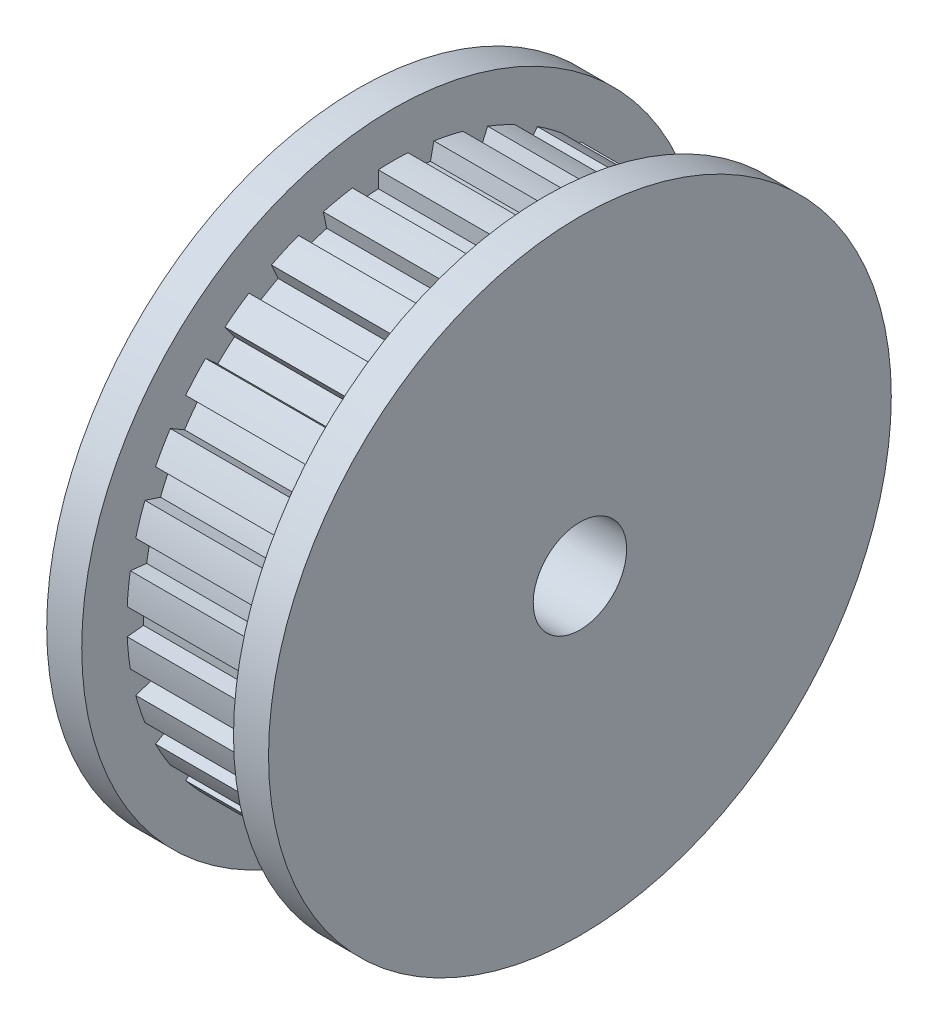
SolidWorks part; units mm, degrees
material "Default"
ref_plane "Top" through (0, 0, 0) normal (0, 0, 1) x (1, 0, 0)
ref_plane "Right" through (0, 0, 0) normal (0, 1, 0) x (1, 0, 0)
ref_plane "Front" through (0, 0, 0) normal (1, 0, 0) x (0, 0, -1)
ref_plane "Plane1" through (-64.6347, 0, 0) normal (-1, 0, 0) x (0, 0, 1)
sketch "Sketch2" plane through (-64.6347, 0, 0) normal (-1, 0, 0) x (0, 0, 1)
  circle A0 centre (18.1528, -99.414) radius 13.335
  circle A1 centre (18.1528, -99.414) radius 2
  dimension "D1" = 4
  dimension "D2" = 26.67
extrude "Boss-Extrude1" add sketch "Sketch2" against normal up to surface (9.5 mm away)
ref_axis "Axis1" through (-22.4133, -99.414, 18.1528) along (-1, 0, 0)
ref_plane "Plane2" through (0, 0, 18.1528) normal (0, 0, -1) x (-1, 0, 0)
sketch "Sketch4" plane through (0, 0, 18.1528) normal (0, 0, -1) x (-1, 0, 0)
  line L0 (52.4933, -99.414) -> (71.4445, -99.414) construction
  line L1 (22.4133, -99.414) -> (89.3613, -99.414) construction
  line L2 (56.6347, -84.904) -> (63.1347, -84.904)
  line L3 (63.1347, -84.904) -> (63.1347, -88.714)
  line L4 (56.6347, -84.904) -> (56.6347, -88.714)
  line L5 (56.6347, -88.714) -> (63.1347, -88.714)
  line L6 (59.8847, -86.714) -> (59.8847, -89.6647) construction
  point P12 (59.8847, -88.714)
  dimension "D1" = 3.81
  dimension "D2" = 6.5
  dimension "D3" = 10.7
revolve "Cut-Revolve1" cut sketch "Sketch4" angle 360 about L0
sketch "Sketch5" plane through (-63.1347, 0, 0) normal (1, 0, 0) x (0, 0, -1)
  line L0 (-18.1528, -99.414) -> (-18.1528, -85.2895) construction
  line L1 (-18.7878, -88.0312) -> (-18.7878, -88.7329)
  line L2 (-17.5178, -88.0312) -> (-17.5178, -88.7329)
  line L3 (-16.4073, -88.148) -> (-16.5532, -88.8343)
  line L4 (-15.165, -88.412) -> (-15.3109, -89.0983)
  line L5 (-14.1031, -88.7571) -> (-14.3885, -89.3981)
  line L6 (-12.9429, -89.2736) -> (-13.2283, -89.9146)
  line L7 (-11.9759, -89.8319) -> (-12.3883, -90.3996)
  line L8 (-10.9484, -90.5784) -> (-11.3608, -91.1461)
  line L9 (-10.1186, -91.3256) -> (-10.64, -91.7951)
  line L10 (-9.2688, -92.2694) -> (-9.7902, -92.7389)
  line L11 (-8.6125, -93.1727) -> (-9.2201, -93.5235)
  line L12 (-7.9775, -94.2726) -> (-8.5851, -94.6234)
  line L13 (-7.5233, -95.2926) -> (-8.1906, -95.5095)
  line L14 (-7.1309, -96.5005) -> (-7.7982, -96.7173)
  line L15 (-6.8987, -97.5927) -> (-7.5965, -97.666)
  line L16 (-6.766, -98.8557) -> (-7.4638, -98.9291)
  line L17 (-6.766, -99.9723) -> (-7.4638, -99.899)
  line L18 (-6.8987, -101.2354) -> (-7.5965, -101.162)
  line L19 (-7.1309, -102.3276) -> (-7.7982, -102.1108)
  line L20 (-7.5233, -103.5354) -> (-8.1906, -103.3186)
  line L21 (-7.9775, -104.5555) -> (-8.5851, -104.2047)
  line L22 (-8.6125, -105.6554) -> (-9.2201, -105.3045)
  line L23 (-9.2688, -106.5587) -> (-9.7902, -106.0892)
  line L24 (-10.1186, -107.5025) -> (-10.64, -107.033)
  line L25 (-10.9484, -108.2497) -> (-11.3608, -107.682)
  line L26 (-11.9759, -108.9962) -> (-12.3883, -108.4285)
  line L27 (-12.9429, -109.5545) -> (-13.2283, -108.9135)
  line L28 (-14.1031, -110.071) -> (-14.3885, -109.43)
  line L29 (-15.165, -110.4161) -> (-15.3109, -109.7298)
  line L30 (-16.4073, -110.6801) -> (-16.5532, -109.9938)
  line L31 (-17.5178, -110.7968) -> (-17.5178, -110.0952)
  line L32 (-18.7878, -110.7968) -> (-18.7878, -110.0952)
  line L33 (-19.8983, -110.6801) -> (-19.7524, -109.9938)
  line L34 (-21.1405, -110.4161) -> (-20.9946, -109.7298)
  line L35 (-22.2025, -110.071) -> (-21.9171, -109.43)
  line L36 (-23.3627, -109.5545) -> (-23.0773, -108.9135)
  line L37 (-24.3297, -108.9962) -> (-23.9173, -108.4285)
  line L38 (-25.3571, -108.2497) -> (-24.9447, -107.682)
  line L39 (-26.1869, -107.5025) -> (-25.6655, -107.033)
  line L40 (-27.0367, -106.5587) -> (-26.5153, -106.0892)
  line L41 (-27.6931, -105.6554) -> (-27.0854, -105.3045)
  line L42 (-28.3281, -104.5555) -> (-27.7204, -104.2047)
  line L43 (-28.7822, -103.5354) -> (-28.1149, -103.3186)
  line L44 (-29.1747, -102.3276) -> (-28.5074, -102.1108)
  line L45 (-29.4068, -101.2354) -> (-28.709, -101.162)
  line L46 (-29.5396, -99.9723) -> (-28.8418, -99.899)
  line L47 (-29.5396, -98.8557) -> (-28.8418, -98.9291)
  line L48 (-29.4068, -97.5927) -> (-28.709, -97.666)
  line L49 (-29.1747, -96.5005) -> (-28.5074, -96.7173)
  line L50 (-28.7822, -95.2926) -> (-28.1149, -95.5095)
  line L51 (-28.3281, -94.2726) -> (-27.7204, -94.6234)
  line L52 (-27.6931, -93.1727) -> (-27.0854, -93.5235)
  line L53 (-27.0367, -92.2694) -> (-26.5153, -92.7389)
  line L54 (-26.1869, -91.3256) -> (-25.6655, -91.7951)
  line L55 (-25.3571, -90.5784) -> (-24.9447, -91.1461)
  line L56 (-24.3297, -89.8319) -> (-23.9173, -90.3996)
  line L57 (-23.3627, -89.2736) -> (-23.0773, -89.9146)
  line L58 (-22.2025, -88.7571) -> (-21.9171, -89.3981)
  line L59 (-21.1405, -88.412) -> (-20.9946, -89.0983)
  line L60 (-19.8983, -88.148) -> (-19.7524, -88.8343)
  arc A0 (-17.5178, -88.7329) -> (-18.7878, -88.7329) centre (-18.1528, -99.414) ccw
  arc A1 (-17.5178, -88.0312) -> (-18.7878, -88.0312) centre (-18.1528, -99.414) ccw
  arc A2 (-15.3109, -89.0983) -> (-16.5532, -88.8343) centre (-18.1528, -99.414) ccw
  arc A3 (-15.165, -88.412) -> (-16.4073, -88.148) centre (-18.1528, -99.414) ccw
  arc A4 (-13.2283, -89.9146) -> (-14.3885, -89.3981) centre (-18.1528, -99.414) ccw
  arc A5 (-12.9429, -89.2736) -> (-14.1031, -88.7571) centre (-18.1528, -99.414) ccw
  arc A6 (-11.3608, -91.1461) -> (-12.3883, -90.3996) centre (-18.1528, -99.414) ccw
  arc A7 (-10.9484, -90.5784) -> (-11.9759, -89.8319) centre (-18.1528, -99.414) ccw
  arc A8 (-9.7902, -92.7389) -> (-10.64, -91.7951) centre (-18.1528, -99.414) ccw
  arc A9 (-9.2688, -92.2694) -> (-10.1186, -91.3256) centre (-18.1528, -99.414) ccw
  arc A10 (-8.5851, -94.6234) -> (-9.2201, -93.5235) centre (-18.1528, -99.414) ccw
  arc A11 (-7.9775, -94.2726) -> (-8.6125, -93.1727) centre (-18.1528, -99.414) ccw
  arc A12 (-7.7982, -96.7173) -> (-8.1906, -95.5095) centre (-18.1528, -99.414) ccw
  arc A13 (-7.1309, -96.5005) -> (-7.5233, -95.2926) centre (-18.1528, -99.414) ccw
  arc A14 (-7.4638, -98.9291) -> (-7.5965, -97.666) centre (-18.1528, -99.414) ccw
  arc A15 (-6.766, -98.8557) -> (-6.8987, -97.5927) centre (-18.1528, -99.414) ccw
  arc A16 (-7.5965, -101.162) -> (-7.4638, -99.899) centre (-18.1528, -99.414) ccw
  arc A17 (-6.8987, -101.2354) -> (-6.766, -99.9723) centre (-18.1528, -99.414) ccw
  arc A18 (-8.1906, -103.3186) -> (-7.7982, -102.1108) centre (-18.1528, -99.414) ccw
  arc A19 (-7.5233, -103.5354) -> (-7.1309, -102.3276) centre (-18.1528, -99.414) ccw
  arc A20 (-9.2201, -105.3045) -> (-8.5851, -104.2047) centre (-18.1528, -99.414) ccw
  arc A21 (-8.6125, -105.6554) -> (-7.9775, -104.5555) centre (-18.1528, -99.414) ccw
  arc A22 (-10.64, -107.033) -> (-9.7902, -106.0892) centre (-18.1528, -99.414) ccw
  arc A23 (-10.1186, -107.5025) -> (-9.2688, -106.5587) centre (-18.1528, -99.414) ccw
  arc A24 (-12.3883, -108.4285) -> (-11.3608, -107.682) centre (-18.1528, -99.414) ccw
  arc A25 (-11.9759, -108.9962) -> (-10.9484, -108.2497) centre (-18.1528, -99.414) ccw
  arc A26 (-14.3885, -109.43) -> (-13.2283, -108.9135) centre (-18.1528, -99.414) ccw
  arc A27 (-14.1031, -110.071) -> (-12.9429, -109.5545) centre (-18.1528, -99.414) ccw
  arc A28 (-16.5532, -109.9938) -> (-15.3109, -109.7298) centre (-18.1528, -99.414) ccw
  arc A29 (-16.4073, -110.6801) -> (-15.165, -110.4161) centre (-18.1528, -99.414) ccw
  arc A30 (-18.7878, -110.0952) -> (-17.5178, -110.0952) centre (-18.1528, -99.414) ccw
  arc A31 (-18.7878, -110.7968) -> (-17.5178, -110.7968) centre (-18.1528, -99.414) ccw
  arc A32 (-20.9946, -109.7298) -> (-19.7524, -109.9938) centre (-18.1528, -99.414) ccw
  arc A33 (-21.1405, -110.4161) -> (-19.8983, -110.6801) centre (-18.1528, -99.414) ccw
  arc A34 (-23.0773, -108.9135) -> (-21.9171, -109.43) centre (-18.1528, -99.414) ccw
  arc A35 (-23.3627, -109.5545) -> (-22.2025, -110.071) centre (-18.1528, -99.414) ccw
  arc A36 (-24.9447, -107.682) -> (-23.9173, -108.4285) centre (-18.1528, -99.414) ccw
  arc A37 (-25.3571, -108.2497) -> (-24.3297, -108.9962) centre (-18.1528, -99.414) ccw
  arc A38 (-26.5153, -106.0892) -> (-25.6655, -107.033) centre (-18.1528, -99.414) ccw
  arc A39 (-27.0367, -106.5587) -> (-26.1869, -107.5025) centre (-18.1528, -99.414) ccw
  circle A40 centre (-18.1528, -99.414) radius 10.7 construction
  arc A41 (-27.7204, -104.2047) -> (-27.0854, -105.3045) centre (-18.1528, -99.414) ccw
  arc A42 (-28.3281, -104.5555) -> (-27.6931, -105.6554) centre (-18.1528, -99.414) ccw
  arc A43 (-28.5074, -102.1108) -> (-28.1149, -103.3186) centre (-18.1528, -99.414) ccw
  arc A44 (-29.1747, -102.3276) -> (-28.7822, -103.5354) centre (-18.1528, -99.414) ccw
  arc A45 (-28.8418, -99.899) -> (-28.709, -101.162) centre (-18.1528, -99.414) ccw
  arc A46 (-29.5396, -99.9723) -> (-29.4068, -101.2354) centre (-18.1528, -99.414) ccw
  arc A47 (-28.709, -97.666) -> (-28.8418, -98.9291) centre (-18.1528, -99.414) ccw
  arc A48 (-29.4068, -97.5927) -> (-29.5396, -98.8557) centre (-18.1528, -99.414) ccw
  arc A49 (-28.1149, -95.5095) -> (-28.5074, -96.7173) centre (-18.1528, -99.414) ccw
  arc A50 (-28.7822, -95.2926) -> (-29.1747, -96.5005) centre (-18.1528, -99.414) ccw
  arc A51 (-27.0854, -93.5235) -> (-27.7204, -94.6234) centre (-18.1528, -99.414) ccw
  arc A52 (-27.6931, -93.1727) -> (-28.3281, -94.2726) centre (-18.1528, -99.414) ccw
  arc A53 (-25.6655, -91.7951) -> (-26.5153, -92.7389) centre (-18.1528, -99.414) ccw
  arc A54 (-26.1869, -91.3256) -> (-27.0367, -92.2694) centre (-18.1528, -99.414) ccw
  arc A55 (-23.9173, -90.3996) -> (-24.9447, -91.1461) centre (-18.1528, -99.414) ccw
  arc A56 (-24.3297, -89.8319) -> (-25.3571, -90.5784) centre (-18.1528, -99.414) ccw
  arc A57 (-21.9171, -89.3981) -> (-23.0773, -89.9146) centre (-18.1528, -99.414) ccw
  arc A58 (-22.2025, -88.7571) -> (-23.3627, -89.2736) centre (-18.1528, -99.414) ccw
  arc A59 (-19.7524, -88.8343) -> (-20.9946, -89.0983) centre (-18.1528, -99.414) ccw
  arc A60 (-19.8983, -88.148) -> (-21.1405, -88.412) centre (-18.1528, -99.414) ccw
  point P85 (-18.1528, -99.414)
  dimension "D2" = 1.27
  dimension "D3" = 1.27
  dimension "D5" = 0.7017
  dimension "D4" = 30
extrude "Boss-Extrude2" add sketch "Sketch5" along normal up to surface (6.5 mm away) up to face at (-56.6347, -112.749, 18.1528)
